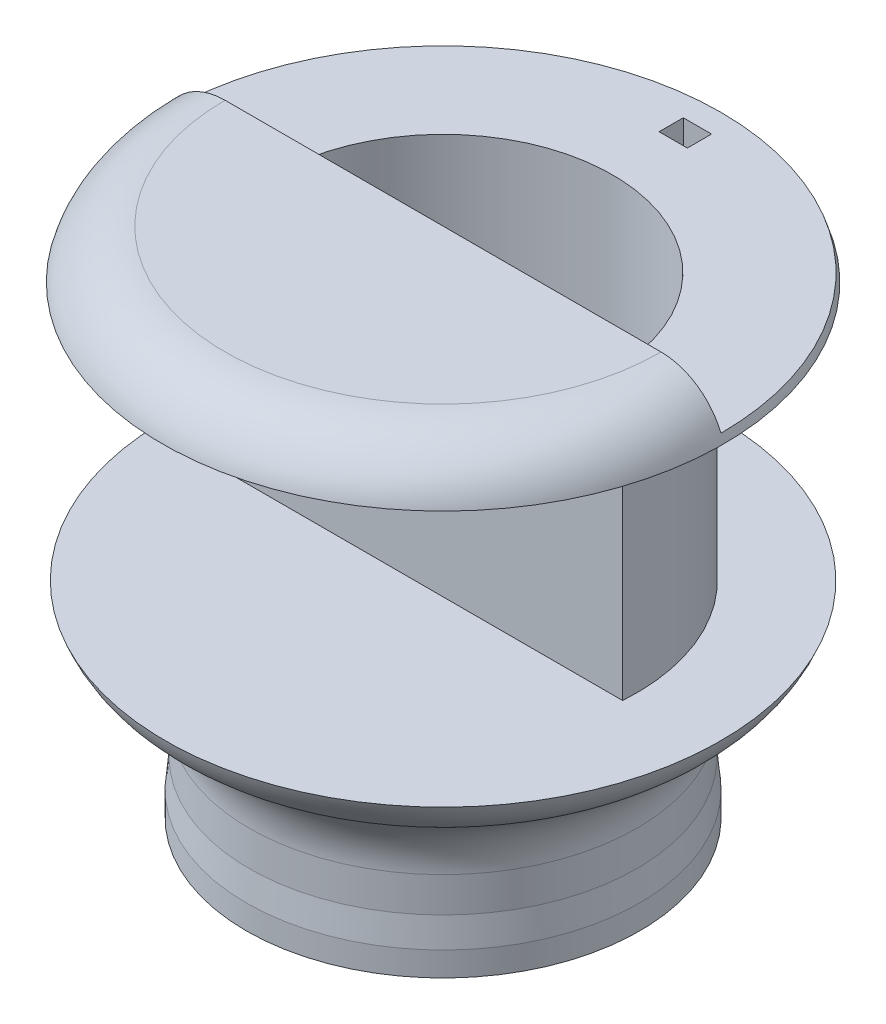
SolidWorks part; units mm, degrees
ref_plane "Front Plane" through (0, 0, 0) normal (0, 0, 1) x (1, 0, 0)
ref_plane "Top Plane" through (0, 0, 0) normal (0, 1, 0) x (1, 0, 0)
ref_plane "Right Plane" through (0, 0, 0) normal (1, 0, 0) x (0, 0, -1)
sketch "Sketch1" plane through (0, 0, 0) normal (0, 0, 1) x (1, 0, 0)
  line L0 (0, 0) -> (0, 90.2242) construction
  line L28 (0, 63.4279) -> (27, 63.4279)
  line L29 (35, 55.4279) -> (35, 28.8468)
  line L30 (22.5, 0) -> (24.35, 0)
  line L31 (24.35, 0) -> (24.35, 3)
  line L32 (24.35, 3) -> (24, 6.5087)
  line L33 (24, 6.5087) -> (24, 10.8398)
  line L34 (28.5399, 19.2175) -> (30.4601, 20.4691)
  line L35 (0, 13) -> (22, 13)
  line L36 (22.5, 12.5) -> (22.5, 0)
  line L37 (0, 13) -> (0, 63.4279)
  arc A0 (22, 13) -> (22.5, 12.5) centre (22, 12.5) cw
  arc A1 (24, 10.8398) -> (28.5399, 19.2175) centre (34, 10.8398) cw
  arc A2 (30.4601, 20.4691) -> (35, 28.8468) centre (25, 28.8468) ccw
  arc A3 (27, 63.4279) -> (35, 55.4279) centre (27, 55.4279) cw
  point P11 (22.9, 63.4279)
  point P18 (22.5, 13)
  point P21 (24, 16.2587)
  point P24 (35, 23.4279)
  point P27 (35, 63.4279)
  point P28 (28.5604, 23.4279)
  point P31 (22.5, 17)
  dimension "D8" = 9.75
  dimension "D9" = 0.5
  dimension "D4" = 1.85
  dimension "D1" = 22.5
  dimension "D10" = 10
  dimension "D11" = 10
  dimension "D12" = 8
  dimension "D2" = 35
  dimension "D3" = 40
  dimension "D5" = 1.5
  dimension "D6" = 3
  dimension "D7" = 13
revolve "Revolve1" add sketch "Sketch1" angle 360 about L0
ref_plane "Plane1" through (0, 13, 0) normal (0, -1, 0) x (-1, 0, 0)
sketch "Sketch18" plane through (0, 0, 0) normal (0, 0, 1) x (1, 0, 0)
  line L0 (0, 0) -> (0, 101.5813) construction
  line L1 (-24.35, 0) -> (24.35, 0) construction
sketch "Sketch3" plane through (0, 0, 0) normal (0, 0, 1) x (1, 0, 0)
  point P0 (1.2404, 19.1989)
ref_point "Point1"
ref_plane "Plane2" through (0, 0, 22.9) normal (0, 0, 1) x (1, 0, 0)
ref_plane "Plane3" through (0, 0, 35) normal (0, 0, 1) x (1, 0, 0)
ref_plane "Plane4" through (0, 55.4279, 0) normal (0, 1, 0) x (1, 0, 0)
sketch "Sketch9" plane through (0, 55.4279, 0) normal (0, 1, 0) x (1, 0, 0)
  line L1 (-24, -1.7631) -> (24, -1.7631)
  arc A2 (-37, -1.6015) -> (37, -2.3985) centre (0, -2) ccw
  arc A3 (-37, -1.6015) -> (37, -2.3985) centre (0, -2) cw
  arc A6 (-24, -1.7631) -> (24, -1.7631) centre (0, -0.0603) cw
  dimension "D1" = 74
  dimension "D3" = 13
  dimension "D4" = 13
ref_plane "Plane5" through (0, 13, 0) normal (0, -1, 0) x (-1, 0, 0)
sketch "Sketch11" plane through (0, 13, 0) normal (0, -1, 0) x (-1, 0, 0)
  line L0 (-21, 0) -> (21, 0)
  arc A1 (-21, 0) -> (21, 0) centre (0, 0) cw
  dimension "D1" = 42
extrude "Cut-Extrude3" cut sketch "Sketch11" against normal blind 60
ref_plane "Plane6" through (0, 0, -35) normal (0, 0, -1) x (-1, 0, 0)
extrude "Cut-Extrude5" cut sketch "Sketch9" against normal blind 30 and the other way blind 2
sketch "Sketch19" plane through (0, 0, 0) normal (1, 0, 0) x (0, 0, -1)
  line L0 (-47.0647, 55.4279) -> (-35.0647, 55.4279)
  line L1 (31.2976, 55.4279) -> (-31.2976, 55.4279) construction
  line L2 (-35.0647, 55.4279) -> (-35.0647, 18.9279)
  line L3 (-35.0647, 18.9279) -> (-47.0647, 18.9279)
  line L4 (-47.0647, 18.9279) -> (-47.0647, 55.4279)
  dimension "D1" = 12
  dimension "D2" = 36.5
revolve "Cut-Revolve2" cut sketch "Sketch19" angle 65 about L0 rebuild error yes other way angle 65
ref_plane "Plane7" through (0, 0, 22.5) normal (0, 0, -1) x (-1, 0, 0)
sketch "Sketch21" plane through (0, 0, 22.5) normal (0, 0, -1) x (-1, 0, 0)
  line L0 (0, 0) -> (0, 101.5813) construction
  line L1 (-1.625, 4) -> (1.625, 4)
  line L2 (-1.625, 4) -> (-1.625, 0)
  line L3 (-1.625, 0) -> (1.625, 0)
  line L4 (1.625, 4) -> (1.625, 0)
  line L5 (-1.625, 4) -> (1.625, 0) construction
  line L6 (-1.625, 0) -> (1.625, 4) construction
  line L7 (-22.5, 0) -> (22.5, 0) construction
  point P0 (0, 2)
  dimension "D1" = 4
  dimension "D2" = 3.25
extrude "Boss-Extrude3" add sketch "Sketch21" along normal blind 1.35
pattern_circular "CirPattern1" count 5 over 360 about axis through (0, 0, 0) along (0, -1, 0) of "Boss-Extrude3"
ref_plane "Plane8" through (0, 20.4691, 0) normal (0, 1, 0) x (1, 0, 0)
sketch "Sketch22" plane through (0, 63.4279, 0) normal (0, 1, 0) x (1, 0, 0)
  line L0 (-40, 0) -> (40, 0)
  arc A0 (-40, 0) -> (40, 0) centre (0, 0) cw
  arc A1 (36.2523, -16.9047) -> (-36.2523, -16.9047) centre (0, 0) ccw construction
extrude "Cut-Extrude9" cut sketch "Sketch22" against normal blind 5
sketch "Sketch23" plane through (0, 0, -35) normal (0, 0, -1) x (-1, 0, 0)
  line L0 (0, 0) -> (0, 101.5813) construction
  line L1 (31.2976, 55.4279) -> (-31.2976, 55.4279) construction
  circle A0 centre (0, 42.1379) radius 10
  dimension "D1" = 20
  dimension "D2" = 13.29
extrude "Cut-Extrude10" cut sketch "Sketch23" against normal blind 10 rebuild error yes
fillet "Fillet1" radius 5 rebuild error yes
sketch "Sketch24" plane through (0, 58.4279, 0) normal (0, 1, 0) x (1, 0, 0)
  line L1 (-6, 32.5) -> (6, 32.5)
  line L2 (-6, 32.5) -> (-6, 27.5)
  line L3 (-6, 27.5) -> (6, 27.5)
  line L4 (6, 32.5) -> (6, 27.5)
  line L5 (-6, 32.5) -> (6, 27.5) construction
  line L6 (-6, 27.5) -> (6, 32.5) construction
  arc A0 (34.4162, 0) -> (-34.4162, 0) centre (0, 0) ccw construction
  point P0 (0, 30)
  dimension "D1" = 30
  dimension "D2" = 5
  dimension "D3" = 12
extrude "Boss-Extrude4" add sketch "Sketch24" against normal blind 8
sketch "Sketch26" plane through (0, 58.4279, 0) normal (0, 1, 0) x (1, 0, 0)
  line L1 (-1.75, 31.5) -> (1.75, 31.5)
  line L2 (-1.75, 31.5) -> (-1.75, 28.5)
  line L3 (-1.75, 28.5) -> (1.75, 28.5)
  line L4 (1.75, 31.5) -> (1.75, 28.5)
  line L5 (-1.75, 31.5) -> (1.75, 28.5) construction
  line L6 (-1.75, 28.5) -> (1.75, 31.5) construction
  arc A0 (34.4162, 0) -> (-34.4162, 0) centre (0, 0) ccw construction
  point P0 (0, 30)
  dimension "D1" = 30
  dimension "D2" = 3
  dimension "D3" = 3.5
extrude "Cut-Extrude11" cut sketch "Sketch26" against normal blind 10
sketch "Sketch27" plane through (6, 0, 0) normal (1, 0, 0) x (0, 0, -1)
  line L0 (32.5, 50.4279) -> (32.5, 57.4279) construction
  line L1 (28.0394, 56.918) -> (31.9606, 56.918)
  line L2 (28.0394, 56.918) -> (28.0394, 50.9378)
  line L3 (28.0394, 50.9378) -> (31.9606, 50.9378)
  line L4 (31.9606, 56.918) -> (31.9606, 50.9378)
  line L5 (28.0394, 56.918) -> (31.9606, 50.9378) construction
  line L6 (28.0394, 50.9378) -> (31.9606, 56.918) construction
  line L7 (27.5, 50.4279) -> (27.5, 57.4279) construction
  line L8 (27.5, 50.4279) -> (32.5, 50.4279) construction
  point P0 (30, 53.9279)
  dimension "D1" = 5
  dimension "D2" = 3.5
extrude "Cut-Extrude12" cut sketch "Sketch27" against normal blind 5
